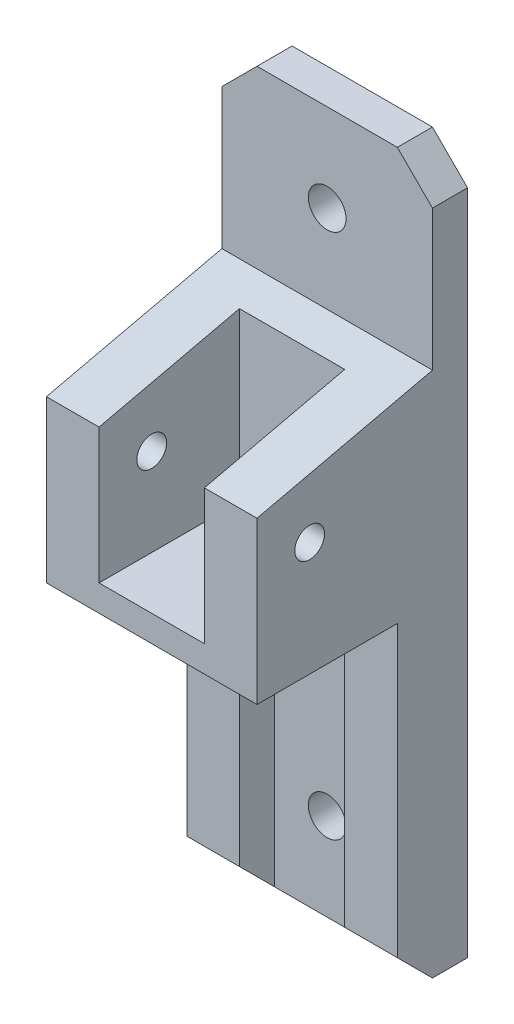
SolidWorks part; units mm, degrees
ref_plane "Plan de face" through (0, 0, 0) normal (0, 0, 1) x (1, 0, 0)
ref_plane "Plan de dessus" through (0, 0, 0) normal (0, 1, 0) x (1, 0, 0)
ref_plane "Plan de droite" through (0, 0, 0) normal (1, 0, 0) x (0, 0, -1)
sketch "Esquisse1" plane through (0, 0, 0) normal (0, 0, 1) x (1, 0, 0)
  line L1 (-12, 40) -> (12, 40)
  line L2 (-12, 40) -> (-12, -40)
  line L3 (-12, -40) -> (12, -40)
  line L4 (12, 40) -> (12, -40)
  line L5 (-12, 40) -> (12, -40) construction
  line L6 (-12, -40) -> (12, 40) construction
  point P0 (0, 0)
  dimension "D1" = 80
  dimension "D2" = 24
extrude "Boss.-Extru.1" add sketch "Esquisse1" along normal blind 4
sketch "Esquisse2" plane through (0, 0, 4) normal (0, 0, 1) x (1, 0, 0)
  line L0 (-12, 40) -> (-12, -40) construction
  line L1 (-12, 20) -> (12, 20)
  line L2 (-12, 20) -> (-12, -3)
  line L3 (-12, -3) -> (12, -3)
  line L4 (12, 20) -> (12, -3)
  line L5 (12, -40) -> (12, 40) construction
  line L6 (12, 40) -> (-12, 40) construction
  dimension "D1" = 23
  dimension "D2" = 20
extrude "Boss.-Extru.2" add sketch "Esquisse2" along normal blind 4
sketch "Esquisse3" plane through (0, 0, 8) normal (0, 0, 1) x (1, 0, 0)
  line L0 (-6, 20) -> (-6, 0)
  line L1 (12, 20) -> (-12, 20) construction
  line L2 (-6, 0) -> (6, 0)
  line L3 (6, 0) -> (6, 20)
  line L4 (6, 20) -> (12, 20)
  line L5 (12, 20) -> (12, -3)
  line L6 (-12, -3) -> (12, -3) construction
  line L7 (12, -3) -> (12, 20) construction
  line L8 (12, -3) -> (-12, -3)
  line L9 (-12, -3) -> (-12, 20)
  line L10 (-12, 20) -> (-6, 20)
  dimension "D1" = 6
  dimension "D2" = 6
  dimension "D3" = 3
extrude "Boss.-Extru.3" add sketch "Esquisse3" along normal blind 16
sketch "Esquisse4" plane through (0, 0, 4) normal (0, 0, 1) x (1, 0, 0)
  line L0 (-12, -3) -> (-12, -40)
  line L1 (-12, -40) -> (-6, -40)
  line L2 (-12, -40) -> (12, -40) construction
  line L3 (-6, -40) -> (-6, -3)
  line L4 (-12, -3) -> (12, -3) construction
  line L5 (-6, -3) -> (-12, -3)
  line L6 (12, -3) -> (6, -3)
  line L7 (6, -3) -> (6, -40)
  line L8 (6, -40) -> (12, -40)
  line L9 (12, -40) -> (12, -3)
  dimension "D1" = 6
  dimension "D2" = 6
extrude "Boss.-Extru.4" add sketch "Esquisse4" along normal blind 4
chamfer "Chanfrein1" distance 4 angle 45 4 edges at (-9, -40, 8) (9, -40, 8) (12, 40, 2) (-12, 40, 2)
chamfer "Chanfrein2" distance 20 angle 13 1 edges at (-9, 20, 24) first distance on face at (2.25, 20, 19.5)
hole_wizard "Dégagement M31" positions "Esquisse6" profile "Esquisse7" hole size "M3" standard "Din" end condition through all
sketch "Esquisse6" plane through (12, 0, 0) normal (1, 0, 0) x (0, 0, -1)
  line L0 (0, -40) -> (0, 36) construction
  line L2 (-4, -40) -> (0, -40) construction
  point P0 (-18, 10)
  dimension "D1" = 18
  dimension "D2" = 50
sketch "Esquisse7" plane through (12, 10, 18) normal (0, 1, 0) x (0, 0, -1)
  line L0 (0, 0) -> (0, 24.0001)
  line L1 (0, 24.0001) -> (1.7, 24.0001)
  line L2 (1.7, 24.0001) -> (1.7, 0)
  line L5 (1.7, 0) -> (0, 0)
  line L11 (0, -6.35) -> (0, 107.95) construction
  dimension "Diamètre du perçage jusqu'au prochain" = 3.4
  dimension "Profondeur du perçage jusqu'au prochain" = 24.0001
hole_wizard "Dégagement M42" positions "Esquisse9" profile "Esquisse10" hole size "M4" standard "Din" end condition through all
sketch "Esquisse9" plane through (0, 0, 4) normal (0, 0, 1) x (1, 0, 0)
  line L0 (0, 40) -> (0, -40) construction
  line L1 (8, 40) -> (-8, 40) construction
  line L2 (-6, -40) -> (6, -40) construction
  point P9 (0, 30)
  point P11 (0, -30)
  dimension "D1" = 10
  dimension "D2" = 10
sketch "Esquisse10" plane through (0, 30, 4) normal (1, 0, 0) x (0, -1, 0)
  line L0 (0, 0) -> (0, 4)
  line L1 (0, 4) -> (2.15, 4)
  line L2 (2.15, 4) -> (2.15, 0)
  line L5 (2.15, 0) -> (0, 0)
  line L11 (0, -6.35) -> (0, 107.95) construction
  dimension "Diamètre du perçage jusqu'au prochain" = 4.3
  dimension "Profondeur du perçage jusqu'au prochain" = 4
sketch "Esquisse11" plane through (-12, 0, 0) normal (-1, 0, 0) x (0, 0, 1)
  circle A0 centre (18, 10) radius 3.2
  dimension "D1" = 6.4
extrude "Enlèv. mat.-Extru.1" cut sketch "Esquisse11" against normal blind 3
